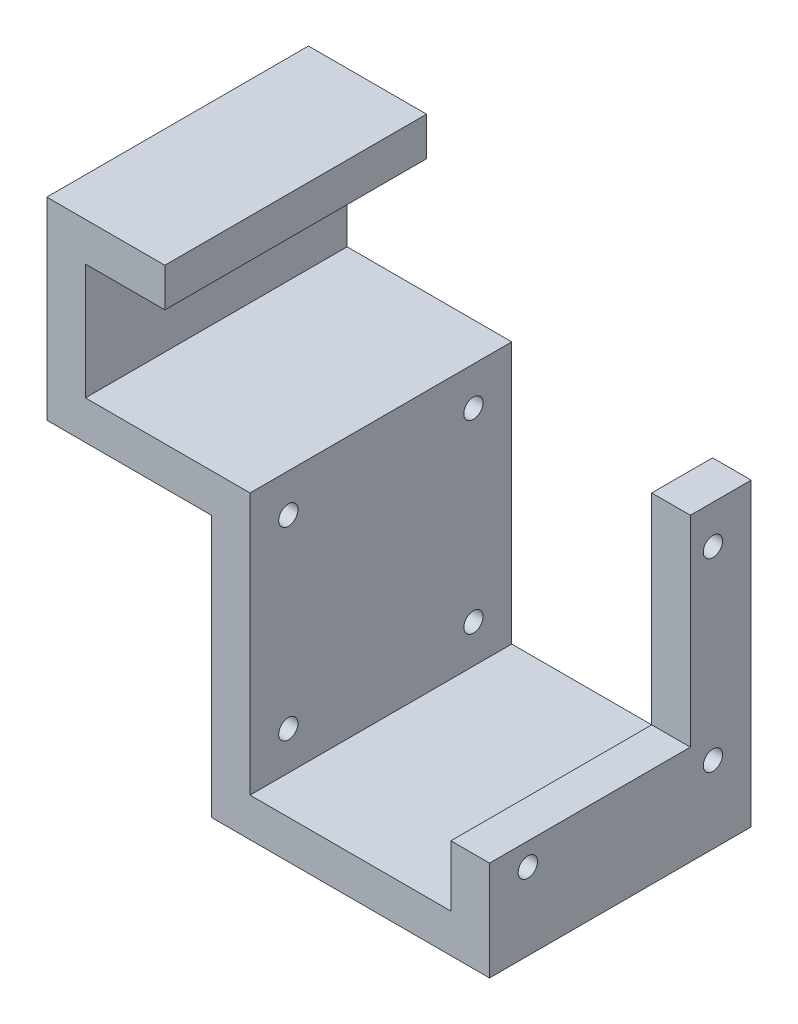
SolidWorks part; units mm, degrees
ref_plane "Front Plane" through (0, 0, 0) normal (0, 0, 1) x (1, 0, 0)
ref_plane "Top Plane" through (0, 0, 0) normal (0, 1, 0) x (1, 0, 0)
ref_plane "Right Plane" through (0, 0, 0) normal (1, 0, 0) x (0, 0, -1)
sketch "Sketch1" plane through (0, 0, 0) normal (0, 0, 1) x (1, 0, 0)
  line L0 (-6.35, -27.85) -> (-6.35, 15.15)
  line L1 (-6.35, 15.15) -> (-33.4, 15.15)
  line L2 (-33.4, 15.15) -> (-33.4, 46.9)
  line L3 (-33.4, 46.9) -> (-14, 46.9)
  line L4 (-14, 46.9) -> (-14, 40.55)
  line L5 (-14, 40.55) -> (-27.05, 40.55)
  line L6 (-27.05, 40.55) -> (-27.05, 21.5)
  line L7 (-27.05, 21.5) -> (0, 21.5)
  line L8 (0, 21.5) -> (0, -21.5)
  line L9 (0, -21.5) -> (33, -21.5)
  line L12 (33, -21.5) -> (33, -27.85)
  line L13 (33, -27.85) -> (-6.35, -27.85)
  line L14 (-27.05, 40.55) -> (11.05, 40.55) construction
  line L15 (-27.05, 40.55) -> (-33.4, 46.9) construction
  line L16 (-27.05, 21.5) -> (-33.4, 15.15) construction
  line L17 (-6.35, 15.15) -> (0, 21.5) construction
  line L18 (0, -21.5) -> (-6.35, -27.85) construction
  line L20 (-27.05, 21.5) -> (-27.05, 40.55) construction
  line L21 (-27.05, 21.5) -> (277.75, 21.5) construction
  line L22 (33, 18.9156) -> (33, -19.0795) construction
  line L23 (33, -21.5) -> (0, -21.5) construction
  line L25 (-14, 43.09) -> (-14, 48.9) construction
  dimension "D1" = 6.35
extrude "Boss-Extrude1" add sketch "Sketch1" against normal up to surface (43 mm away) contours L6 L7 L8 L9 L12 L13 L0 L1 L2 L3 L4 L5
sketch "Sketch2" plane through (33, 0, 0) normal (1, 0, 0) x (0, 0, -1)
  line L0 (43, -27.85) -> (0, -27.85) construction
  line L1 (33, -27.85) -> (43, -27.85)
  line L2 (33, -27.85) -> (33, 21.5)
  line L3 (33, 21.5) -> (43, 21.5)
  line L4 (43, -27.85) -> (43, 21.5)
  line L5 (33, -27.85) -> (43, 21.5) construction
  line L6 (33, 21.5) -> (43, -27.85) construction
  line L7 (43, 21.5) -> (0, 21.5) construction
  line L9 (0, -27.85) -> (33, -27.85)
  line L10 (0, -27.85) -> (0, -11.5)
  line L11 (0, -11.5) -> (33, -11.5)
  line L12 (33, -27.85) -> (33, -11.5)
  line L13 (0, -27.85) -> (33, -11.5) construction
  line L14 (0, -11.5) -> (33, -27.85) construction
  circle A0 centre (21.5, 0) radius 11.5 construction
  circle A2 centre (6.2942, -15.2058) radius 1.5
  circle A3 centre (36.7058, -15.2058) radius 1.5
  circle A4 centre (36.7058, 15.2058) radius 1.5
  circle A5 centre (6.2942, -15.2058) radius 1.5 construction
  point P4 (38, -3.175)
  point P17 (16.5, -19.675)
  line M5 (0, -27.85) -> (43, -27.85)
  line M6 (43, -27.85) -> (43, -21.5)
  line M7 (43, -21.5) -> (0, -21.5)
  line M8 (0, -21.5) -> (0, -27.85)
extrude "Boss-Extrude2" add sketch "Sketch2" along normal blind 6.35 contours L2 M5 M7 M8 | L11 L10 L2 A2 M7 | L2 M5 M6 M7 | L4 L3 L2 A4 A3 M7 region at (33, -24.675, -38) region at (33, -24.675, -16.5) region at (33, -16.5283, -16.7234) region at (33, 0, -38.044)
sketch "Sketch3" plane through (-6.35, 0, 0) normal (1, 0, 0) x (0, 0, -1)
  line L0 (0, 15.2058) -> (6.2942, 15.2058) construction
  line L1 (0, 21.5) -> (0, -21.5) construction
  circle A0 centre (6.2942, -15.2058) radius 1.5875
  circle A1 centre (6.2942, 15.2058) radius 1.5875
  circle A8 centre (36.7058, 15.2058) radius 1.5875
  circle A9 centre (36.7058, -15.2058) radius 1.5875
  point P12 (0, 0)
  dimension "D1" = 3.175
extrude "Cut-Extrude1" cut sketch "Sketch3" against normal blind 12.7 and the other way through all
